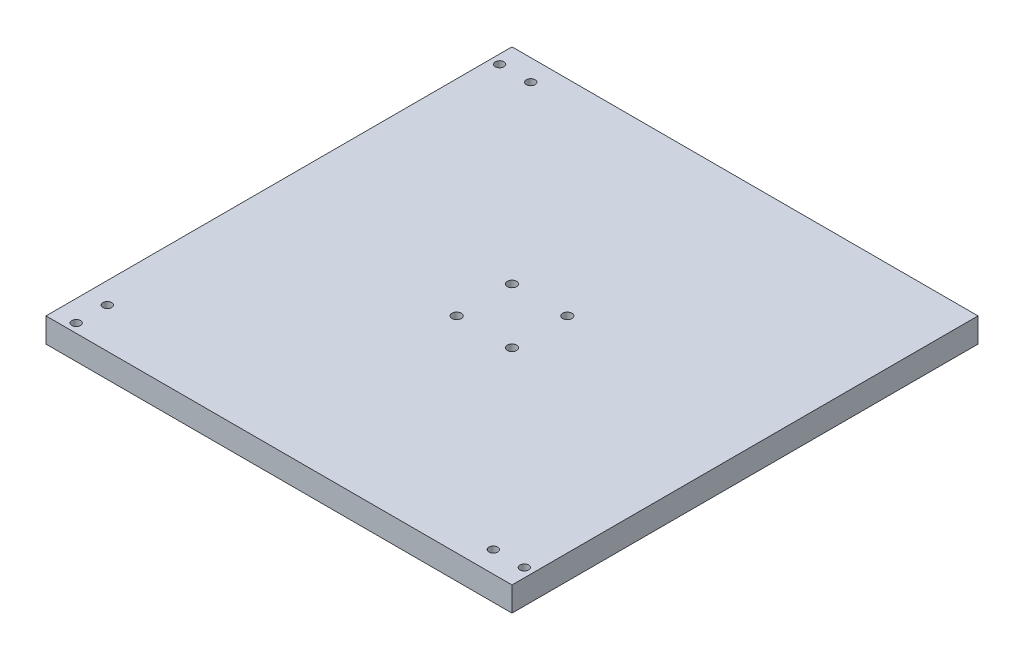
SolidWorks part; units mm, degrees
ref_plane "Front Plane" through (0, 0, 0) normal (0, 0, 1) x (1, 0, 0)
ref_plane "Top Plane" through (0, 0, 0) normal (0, 1, 0) x (1, 0, 0)
ref_plane "Right Plane" through (0, 0, 0) normal (1, 0, 0) x (0, 0, -1)
sketch "Sketch1" plane through (0, 0, 0) normal (0, 1, 0) x (1, 0, 0)
  line L1 (-95.25, -95.25) -> (95.25, -95.25)
  line L2 (-95.25, -95.25) -> (-95.25, 95.25)
  line L3 (-95.25, 95.25) -> (95.25, 95.25)
  line L4 (95.25, -95.25) -> (95.25, 95.25)
  line L5 (-15.875, -15.875) -> (15.875, -15.875)
  line L6 (-15.875, -15.875) -> (-15.875, 15.875)
  line L7 (-15.875, 15.875) -> (15.875, 15.875)
  line L8 (15.875, -15.875) -> (15.875, 15.875)
  circle A0 centre (-11.303, 11.303) radius 1.905
  circle A1 centre (-11.303, -11.303) radius 1.905
  circle A2 centre (11.303, 11.303) radius 1.905
  circle A3 centre (11.303, -11.303) radius 1.905
  circle A4 centre (-78.9, 86.55) radius 1.778
  circle A5 centre (-91.6, 86.55) radius 1.778
  circle A6 centre (91.6, -86.55) radius 1.778
  circle A7 centre (78.9, -86.55) radius 1.778
  circle A8 centre (-86.55, -78.9) radius 1.778
  circle A9 centre (-86.55, -91.6) radius 1.778
  circle A10 centre (0, 0) radius 6.35
  point P0 (0, 0)
  point P6 (0, 0)
  point P19 (-85.25, 92.9)
  point P24 (85.25, -92.9)
  point P29 (-92.9, -85.25)
  dimension "D5" = 4.572
  dimension "D10" = 12.7
  dimension "D18" = 12.7
  dimension "D1" = 190.5
  dimension "D2" = 190.5
  dimension "D3" = 31.75
  dimension "D4" = 31.75
  dimension "D6" = 4.572
  dimension "D7" = 4.572
  dimension "D8" = 92.9
  dimension "D9" = 85.25
  dimension "D11" = 4.572
  dimension "D12" = 6.35
  dimension "D13" = 6.35
  dimension "D14" = 92.9
  dimension "D15" = 85.25
  dimension "D16" = 6.35
  dimension "D17" = 6.35
  dimension "D19" = 85.25
  dimension "D20" = 92.9
  dimension "D21" = 6.35
  dimension "D22" = 6.35
  dimension "D23" = 12.7
extrude "Boss-Extrude1" add sketch "Sketch1" along normal blind 10 contours L4 L3 L2 L1 | A7 | A6 | A8 | A9 | A4 | A5 | A1 | A3 | A0 | A2
